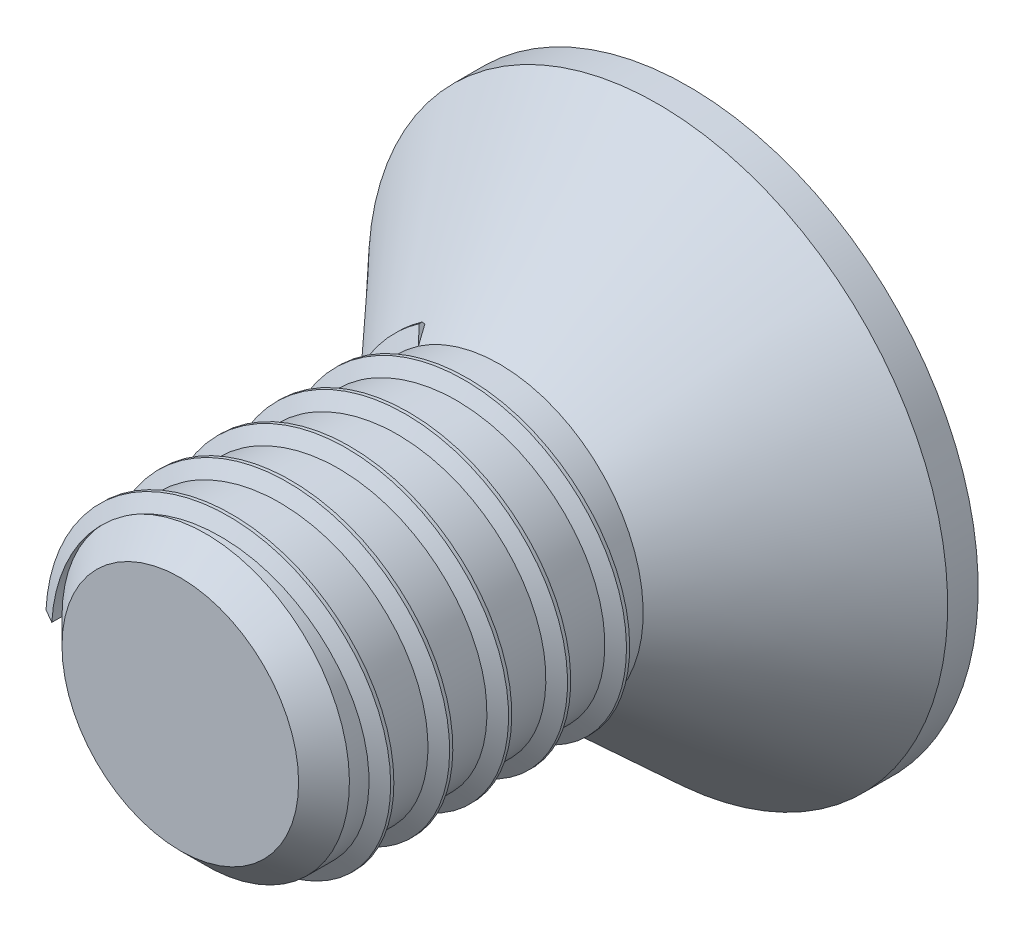
SolidWorks part; units mm, degrees
material "Acero aleado"
ref_plane "Alzado" through (0, 0, 0) normal (0, 0, 1) x (1, 0, 0)
ref_plane "Planta" through (0, 0, 0) normal (0, 1, 0) x (1, 0, 0)
ref_plane "Vista lateral" through (0, 0, 0) normal (1, 0, 0) x (0, 0, -1)
sketch "Croquis1" plane through (0, 0, 0) normal (0, 0, 1) x (1, 0, 0)
  circle A0 centre (0, 0) radius 1.4141
  dimension "D1" = 2.8281
extrude "Saliente-Extruir3" add sketch "Croquis1" along normal blind 3.14 contours A0
sketch "Croquis5" plane through (0, 0, 0) normal (1, 0, 0) x (0, 0, -1)
  line L0 (0, 0) -> (1.86, 0) construction
  line L1 (1.86, 2.85) -> (1.86, -2.85) construction
  line L2 (1.86, 2.85) -> (1.56, 2.85)
  line L3 (1.56, 2.85) -> (0, 1.4141)
  line L8 (1.86, 2.85) -> (1.86, 0)
  line L9 (1.86, 0) -> (0, 0)
  line L10 (0, 0) -> (0, 1.4141)
  point P5 (1.86, 0)
  dimension "D1" = 1.86
  dimension "D2" = 5.7
  dimension "D3" = 0.3
revolve "Revolución1" add sketch "Croquis5" angle 360 about L9
chamfer "Chaflán1" distance 0.25 angle 45 1 edges at (1.4141, 0, 3.14)
thread "Rosca1" pitch 0.25 method extrude profile "Perfil de rosca1" start angle 0, offset 0.1, length 0, pitch 0.58, diameter 2.8281
ref_plane "Plano1" through (-1.4141, 0, 2.99) normal (0, -1, 0) x (-1, 0, 0)
sketch "Perfil de rosca1" plane through (-1.4141, 0, 2.99) normal (0, -1, 0) x (-1, 0, 0)
  line L0 (0, 0) -> (0, 0.25) construction
  line L1 (0, 0) -> (0.1353, 0.0781)
  line L2 (0.1353, 0.0781) -> (0.1353, 0.1094)
  line L3 (0.1353, 0.1094) -> (0, 0.1875)
  line L4 (0.1353, 0.0937) -> (0, 0.0937) construction
  line L11 (0, 0) -> (0, 0.1875)
  point P2 (0, 0)
  dimension "Pitch" = 0.25
  dimension "Profile_Angle" = 60
  dimension "Profile_Land" = 0.0312
  dimension "Profile_Height" = 0.1353
sketch "Croquis16" plane through (0, 0, -1.86) normal (0, 0, -1) x (-1, 0, 0)
  line L1 (1.05, -0.6062) -> (1.05, 0.6062)
  line L2 (1.05, 0.6062) -> (0, 1.2124)
  line L3 (0, 1.2124) -> (-1.05, 0.6062)
  line L4 (-1.05, 0.6062) -> (-1.05, -0.6062)
  line L5 (-1.05, -0.6062) -> (0, -1.2124)
  line L6 (0, -1.2124) -> (1.05, -0.6062)
  circle A0 centre (0, 0) radius 1.05 construction
  dimension "D1" = 2.1
extrude "Cortar-Extruir1" cut sketch "Croquis16" against normal blind 1.5
chamfer "Chaflán2" distance 0.15 angle 45 6 edges at (0.525, -0.9093, -0.36) (1.05, 0, -0.36) (0.525, 0.9093, -0.36) (-0.525, 0.9093, -0.36) (-1.05, 0, -0.36) (-0.525, -0.9093, -0.36)
